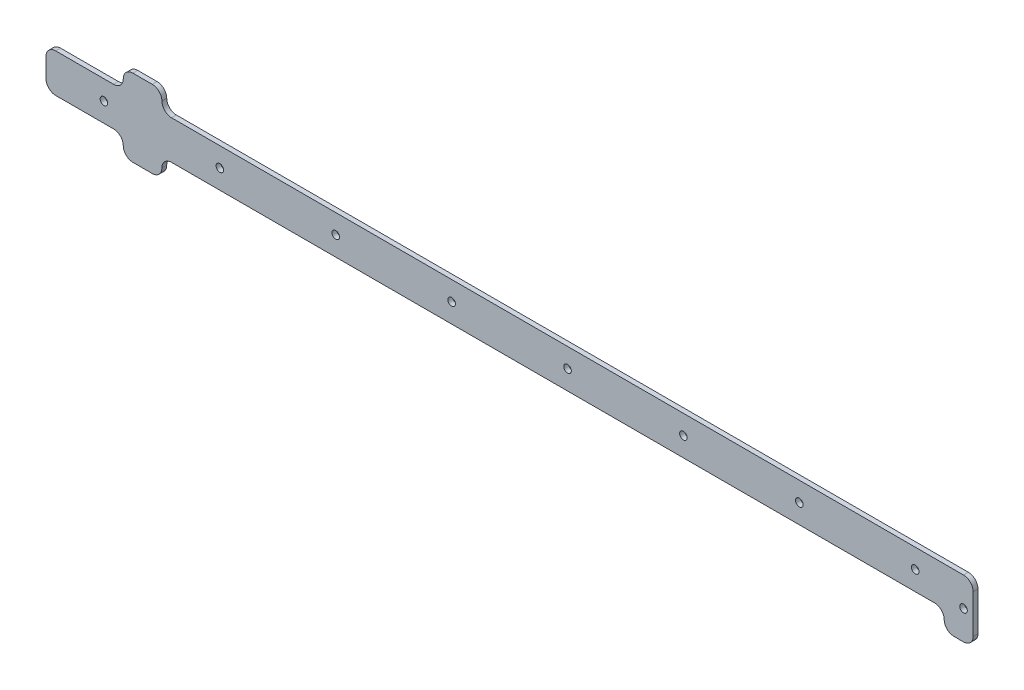
SolidWorks part; units mm, degrees
material "PC High Viscosity"
ref_plane "Front Plane" through (0, 0, 0) normal (0, 0, 1) x (1, 0, 0)
ref_plane "Top Plane" through (0, 0, 0) normal (0, 1, 0) x (1, 0, 0)
ref_plane "Right Plane" through (0, 0, 0) normal (1, 0, 0) x (0, 0, -1)
sketch "Sketch1" plane through (0, 0, 0) normal (0, 0, 1) x (1, 0, 0)
  line L0 (50.8, 0) -> (50.8, -12.7)
  line L1 (0, 0) -> (590.55, 0)
  line L2 (0, 0) -> (0, 25.4)
  line L3 (0, 25.4) -> (609.6, 25.4)
  line L4 (609.6, 0) -> (609.6, 25.4)
  line L5 (50.8, 38.1) -> (76.2, 38.1)
  line L6 (76.2, 38.1) -> (76.2, 25.4)
  line L7 (50.8, 38.1) -> (50.8, 25.4)
  line L8 (76.2, 0) -> (76.2, -12.7)
  line L9 (76.2, -12.7) -> (50.8, -12.7)
  line L10 (590.55, 0) -> (590.55, -12.7)
  line L11 (609.6, 10.0162) -> (603.25, 13.6823) construction
  line L12 (603.25, 13.6823) -> (596.9, 10.0162) construction
  line L13 (596.9, 10.0162) -> (596.9, 2.6838) construction
  line L14 (596.9, 2.6838) -> (603.25, -0.9823) construction
  line L15 (603.25, -0.9823) -> (609.6, 2.6838) construction
  line L16 (609.6, 2.6838) -> (609.6, 10.0162) construction
  line L17 (609.6, 0) -> (609.6, -12.7)
  line L18 (609.6, -12.7) -> (590.55, -12.7)
  circle A0 centre (603.25, 6.35) radius 2.4892
  circle A1 centre (603.25, 6.35) radius 6.35 construction
  dimension "D5" = 4.9784
  dimension "D6" = 12.7
  dimension "D7" = 12.7
  dimension "D1" = 609.6
  dimension "D2" = 25.4
  dimension "D3" = 25.4
  dimension "D4" = 50.8
  dimension "D8" = 19.05
  dimension "D9" = 12.7
extrude "Boss-Extrude1" add sketch "Sketch1" along normal blind 3.175 contours L6 L5 L3 | L1 L4 L3 L2 A0 | L9 L8 L1 region at (63.5, -6.35, 0) region at (308.9784, 12.4144, 0) region at (63.5, 31.75, 0)
fillet "Fillet2" radius 6.35 14 edges at (76.2, 38.1, 1.5875) (76.2, 25.4, 1.5875) (609.6, 25.4, 1.5875) (76.2, 0, 1.5875) (76.2, -12.7, 1.5875) (50.8, -12.7, 1.5875) (50.8, 0, 1.5875) (0, 0, 1.5875) (50.8, 38.1, 1.5875) (50.8, 25.4, 1.5875) (0, 25.4, 1.5875) (590.55, 0, 1.5875) (590.55, -12.7, 1.5875) (609.6, -12.7, 1.5875)
sketch "Sketch2" plane through (0, 0, 3.175) normal (0, 0, 1) x (1, 0, 0)
  line L0 (82.55, 25.4) -> (603.25, 25.4) construction
  line L1 (609.6, 19.05) -> (609.6, -6.35) construction
  circle A0 centre (571.5, 12.7) radius 2.4892
  dimension "D1" = 4.9784
  dimension "D2" = 12.7
  dimension "D3" = 38.1
extrude "Cut-Extrude1" cut sketch "Sketch2" against normal through all
pattern_linear "LPattern1" count 8 spacing 76.2 along (-1, 0, 0) of "Cut-Extrude1"
